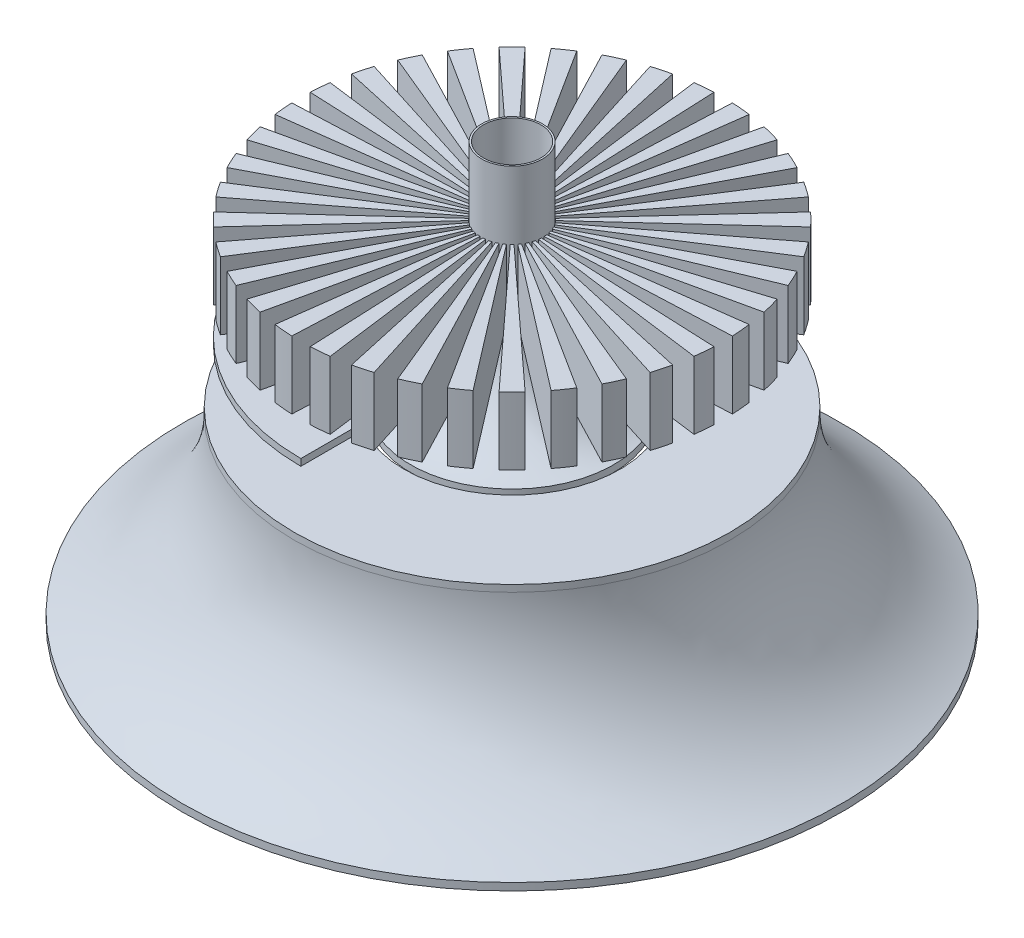
SolidWorks part; units mm, degrees
other "光纤导管"
ref_plane "前视基准面" through (0, 0, 0) normal (0, 0, 1) x (1, 0, 0)
ref_plane "上视基准面" through (0, 0, 0) normal (0, 1, 0) x (1, 0, 0)
ref_plane "右视基准面" through (0, 0, 0) normal (1, 0, 0) x (0, 0, -1)
sketch "草图2" plane through (0, 0, 0) normal (0, 1, 0) x (1, 0, 0)
  circle A0 centre (0, 0) radius 8.5
  circle A1 centre (0, 0) radius 8.5
  circle A2 centre (0, 0) radius 9
extrude "光纤导管" add sketch "草图2" along normal blind 40 contours A2 A0 region at (-8.7454, 0, 0)
sketch "草图5" plane through (0, 0, 0) normal (0, 1, 0) x (1, 0, 0)
  line L0 (0, 23.5527) -> (0, -24.5414) construction
  circle A0 centre (0, 0) radius 9
  circle A1 centre (0, 0) radius 30
sketch "草图6" plane through (0, 0, 0) normal (0, 1, 0) x (1, 0, 0)
  line L0 (0, 0) -> (0, 45.2005) construction
  line L1 (-1.1868, -9.0148) -> (-8.1579, -61.9653)
  line L2 (1.1868, 9.0148) -> (8.1579, 61.9653)
  line L3 (0.3966, 9.0839) -> (2.7262, 62.4405)
  line L4 (1.968, 8.877) -> (13.5275, 61.0185)
  line L5 (2.7342, 8.6717) -> (18.7941, 59.6073)
  line L6 (3.4796, 8.4004) -> (23.9177, 57.7425)
  line L7 (4.1985, 8.0652) -> (28.8593, 55.4382)
  line L8 (4.8854, 7.6686) -> (33.5812, 52.712)
  line L9 (5.5352, 7.2136) -> (38.0476, 49.5846)
  line L10 (8.6717, 2.7342) -> (59.6073, 18.7941)
  line L11 (6.1428, 6.7037) -> (42.2244, 46.0798)
  line L12 (6.7037, 6.1428) -> (46.0798, 42.2244)
  line L13 (7.2136, 5.5352) -> (49.5846, 38.0476)
  line L14 (7.6686, 4.8854) -> (52.712, 33.5812)
  line L15 (7.2136, 5.5352) -> (49.5846, 38.0476)
  line L16 (8.0652, 4.1985) -> (55.4382, 28.8593)
  line L17 (8.4004, 3.4796) -> (57.7425, 23.9177)
  line L18 (8.877, 1.968) -> (61.0185, 13.5275)
  line L19 (9.0148, 1.1868) -> (61.9653, 8.1579)
  line L20 (9.0839, 0.3966) -> (62.4405, 2.7262)
  line L21 (-0.3966, -9.0839) -> (-2.7262, -62.4405)
  line L22 (-1.968, -8.877) -> (-13.5275, -61.0185)
  line L23 (-2.7342, -8.6717) -> (-18.7941, -59.6073)
  line L24 (-3.4796, -8.4004) -> (-23.9177, -57.7425)
  line L25 (-4.1985, -8.0652) -> (-28.8593, -55.4382)
  line L26 (-4.8854, -7.6686) -> (-33.5812, -52.712)
  line L27 (-5.5352, -7.2136) -> (-38.0476, -49.5846)
  line L28 (-8.6717, -2.7342) -> (-59.6073, -18.7941)
  line L29 (-6.1428, -6.7037) -> (-42.2244, -46.0798)
  line L30 (-6.7037, -6.1428) -> (-46.0798, -42.2244)
  line L31 (-7.2136, -5.5352) -> (-49.5846, -38.0476)
  line L32 (-7.6686, -4.8854) -> (-52.712, -33.5812)
  line L33 (-7.2136, -5.5352) -> (-49.5846, -38.0476)
  line L34 (-8.0652, -4.1985) -> (-55.4382, -28.8593)
  line L35 (-8.4004, -3.4796) -> (-57.7425, -23.9177)
  line L36 (-8.877, -1.968) -> (-61.0185, -13.5275)
  line L37 (-9.0148, -1.1868) -> (-61.9653, -8.1579)
  line L38 (-9.0839, -0.3966) -> (-62.4405, -2.7262)
  line L39 (-9.0839, 0.3966) -> (-62.4405, 2.7262)
  line L40 (-9.0148, 1.1868) -> (-61.9653, 8.1579)
  line L41 (-8.877, 1.968) -> (-61.0185, 13.5275)
  line L42 (-8.4004, 3.4796) -> (-57.7425, 23.9177)
  line L43 (-8.0652, 4.1985) -> (-55.4382, 28.8593)
  line L44 (-7.2136, 5.5352) -> (-49.5846, 38.0476)
  line L45 (-7.6686, 4.8854) -> (-52.712, 33.5812)
  line L46 (-7.2136, 5.5352) -> (-49.5846, 38.0476)
  line L47 (-6.7037, 6.1428) -> (-46.0798, 42.2244)
  line L48 (-6.1428, 6.7037) -> (-42.2244, 46.0798)
  line L49 (-8.6717, 2.7342) -> (-59.6073, 18.7941)
  line L50 (-5.5352, 7.2136) -> (-38.0476, 49.5846)
  line L51 (-4.8854, 7.6686) -> (-33.5812, 52.712)
  line L52 (-4.1985, 8.0652) -> (-28.8593, 55.4382)
  line L53 (-3.4796, 8.4004) -> (-23.9177, 57.7425)
  line L54 (-2.7342, 8.6717) -> (-18.7941, 59.6073)
  line L55 (-1.968, 8.877) -> (-13.5275, 61.0185)
  line L56 (-0.3966, 9.0839) -> (-2.7262, 62.4405)
  line L57 (-1.1868, 9.0148) -> (-8.1579, 61.9653)
  line L60 (9.0839, -0.3966) -> (62.4405, -2.7262)
  line L61 (9.0148, -1.1868) -> (61.9653, -8.1579)
  line L62 (8.877, -1.968) -> (61.0185, -13.5275)
  line L63 (8.4004, -3.4796) -> (57.7425, -23.9177)
  line L64 (8.0652, -4.1985) -> (55.4382, -28.8593)
  line L65 (7.2136, -5.5352) -> (49.5846, -38.0476)
  line L66 (7.6686, -4.8854) -> (52.712, -33.5812)
  line L67 (7.2136, -5.5352) -> (49.5846, -38.0476)
  line L68 (6.7037, -6.1428) -> (46.0798, -42.2244)
  line L69 (6.1428, -6.7037) -> (42.2244, -46.0798)
  line L70 (8.6717, -2.7342) -> (59.6073, -18.7941)
  line L71 (5.5352, -7.2136) -> (38.0476, -49.5846)
  line L72 (4.8854, -7.6686) -> (33.5812, -52.712)
  line L73 (4.1985, -8.0652) -> (28.8593, -55.4382)
  line L74 (3.4796, -8.4004) -> (23.9177, -57.7425)
  line L75 (2.7342, -8.6717) -> (18.7941, -59.6073)
  line L76 (1.968, -8.877) -> (13.5275, -61.0185)
  line L77 (0.3966, -9.0839) -> (2.7262, -62.4405)
  line L78 (1.1868, -9.0148) -> (8.1579, -61.9653)
  arc A0 (-62.4405, -2.7262) -> (-61.9653, -8.1579) centre (0, 0) ccw
  arc A1 (62.4405, 2.7262) -> (61.9653, 8.1579) centre (0, 0) ccw
  arc A2 (8.1579, 61.9653) -> (2.7262, 62.4405) centre (0, 0) ccw
  arc A3 (9.0839, 0.3966) -> (9.0148, 1.1868) centre (0, 0) ccw
  arc A4 (18.7941, 59.6073) -> (13.5275, 61.0185) centre (0, 0) ccw
  arc A5 (28.8593, 55.4382) -> (23.9177, 57.7425) centre (0, 0) ccw
  arc A6 (38.0476, 49.5846) -> (33.5812, 52.712) centre (0, 0) ccw
  arc A7 (5.5352, 7.2136) -> (4.8854, 7.6686) centre (0, 0) ccw
  arc A8 (1.1868, 9.0148) -> (0.3966, 9.0839) centre (0, 0) ccw
  arc A9 (2.7342, 8.6717) -> (1.968, 8.877) centre (0, 0) ccw
  arc A10 (4.1985, 8.0652) -> (3.4796, 8.4004) centre (0, 0) ccw
  arc A11 (46.0798, 42.2244) -> (42.2244, 46.0798) centre (0, 0) ccw
  arc A12 (6.7037, 6.1428) -> (6.1428, 6.7037) centre (0, 0) ccw
  arc A13 (52.712, 33.5812) -> (49.5846, 38.0476) centre (0, 0) ccw
  arc A14 (7.6686, 4.8854) -> (7.2136, 5.5352) centre (0, 0) ccw
  arc A15 (57.7425, 23.9177) -> (55.4382, 28.8593) centre (0, 0) ccw
  arc A16 (8.4004, 3.4796) -> (8.0652, 4.1985) centre (0, 0) ccw
  arc A17 (61.0185, 13.5275) -> (59.6073, 18.7941) centre (0, 0) ccw
  arc A18 (8.877, 1.968) -> (8.6717, 2.7342) centre (0, 0) ccw
  arc A19 (-8.1579, -61.9653) -> (-2.7262, -62.4405) centre (0, 0) ccw
  arc A20 (-9.0839, -0.3966) -> (-9.0148, -1.1868) centre (0, 0) ccw
  arc A21 (-18.7941, -59.6073) -> (-13.5275, -61.0185) centre (0, 0) ccw
  arc A22 (-28.8593, -55.4382) -> (-23.9177, -57.7425) centre (0, 0) ccw
  arc A23 (-38.0476, -49.5846) -> (-33.5812, -52.712) centre (0, 0) ccw
  arc A24 (-5.5352, -7.2136) -> (-4.8854, -7.6686) centre (0, 0) ccw
  arc A25 (-1.1868, -9.0148) -> (-0.3966, -9.0839) centre (0, 0) ccw
  arc A26 (-2.7342, -8.6717) -> (-1.968, -8.877) centre (0, 0) ccw
  arc A27 (-4.1985, -8.0652) -> (-3.4796, -8.4004) centre (0, 0) ccw
  arc A28 (-46.0798, -42.2244) -> (-42.2244, -46.0798) centre (0, 0) ccw
  arc A29 (-6.7037, -6.1428) -> (-6.1428, -6.7037) centre (0, 0) ccw
  arc A30 (-52.712, -33.5812) -> (-49.5846, -38.0476) centre (0, 0) ccw
  arc A31 (-7.6686, -4.8854) -> (-7.2136, -5.5352) centre (0, 0) ccw
  arc A32 (-57.7425, -23.9177) -> (-55.4382, -28.8593) centre (0, 0) ccw
  arc A33 (-8.4004, -3.4796) -> (-8.0652, -4.1985) centre (0, 0) ccw
  arc A34 (-61.0185, -13.5275) -> (-59.6073, -18.7941) centre (0, 0) ccw
  arc A35 (-8.877, -1.968) -> (-8.6717, -2.7342) centre (0, 0) ccw
  arc A36 (-8.877, 1.968) -> (-8.6717, 2.7342) centre (0, 0) cw
  arc A37 (-61.0185, 13.5275) -> (-59.6073, 18.7941) centre (0, 0) cw
  arc A38 (-8.4004, 3.4796) -> (-8.0652, 4.1985) centre (0, 0) cw
  arc A39 (-57.7425, 23.9177) -> (-55.4382, 28.8593) centre (0, 0) cw
  arc A40 (-7.6686, 4.8854) -> (-7.2136, 5.5352) centre (0, 0) cw
  arc A41 (-52.712, 33.5812) -> (-49.5846, 38.0476) centre (0, 0) cw
  arc A42 (-6.7037, 6.1428) -> (-6.1428, 6.7037) centre (0, 0) cw
  arc A43 (-46.0798, 42.2244) -> (-42.2244, 46.0798) centre (0, 0) cw
  arc A44 (-4.1985, 8.0652) -> (-3.4796, 8.4004) centre (0, 0) cw
  arc A45 (-2.7342, 8.6717) -> (-1.968, 8.877) centre (0, 0) cw
  arc A46 (-1.1868, 9.0148) -> (-0.3966, 9.0839) centre (0, 0) cw
  arc A47 (-5.5352, 7.2136) -> (-4.8854, 7.6686) centre (0, 0) cw
  arc A48 (-38.0476, 49.5846) -> (-33.5812, 52.712) centre (0, 0) cw
  arc A49 (-28.8593, 55.4382) -> (-23.9177, 57.7425) centre (0, 0) cw
  arc A50 (-18.7941, 59.6073) -> (-13.5275, 61.0185) centre (0, 0) cw
  arc A51 (-9.0839, 0.3966) -> (-9.0148, 1.1868) centre (0, 0) cw
  arc A52 (-8.1579, 61.9653) -> (-2.7262, 62.4405) centre (0, 0) cw
  arc A53 (-62.4405, 2.7262) -> (-61.9653, 8.1579) centre (0, 0) cw
  arc A55 (8.877, -1.968) -> (8.6717, -2.7342) centre (0, 0) cw
  arc A56 (61.0185, -13.5275) -> (59.6073, -18.7941) centre (0, 0) cw
  arc A57 (8.4004, -3.4796) -> (8.0652, -4.1985) centre (0, 0) cw
  arc A58 (57.7425, -23.9177) -> (55.4382, -28.8593) centre (0, 0) cw
  arc A59 (7.6686, -4.8854) -> (7.2136, -5.5352) centre (0, 0) cw
  arc A60 (52.712, -33.5812) -> (49.5846, -38.0476) centre (0, 0) cw
  arc A61 (6.7037, -6.1428) -> (6.1428, -6.7037) centre (0, 0) cw
  arc A62 (46.0798, -42.2244) -> (42.2244, -46.0798) centre (0, 0) cw
  arc A63 (4.1985, -8.0652) -> (3.4796, -8.4004) centre (0, 0) cw
  arc A64 (2.7342, -8.6717) -> (1.968, -8.877) centre (0, 0) cw
  arc A65 (1.1868, -9.0148) -> (0.3966, -9.0839) centre (0, 0) cw
  arc A66 (5.5352, -7.2136) -> (4.8854, -7.6686) centre (0, 0) cw
  arc A67 (38.0476, -49.5846) -> (33.5812, -52.712) centre (0, 0) cw
  arc A68 (28.8593, -55.4382) -> (23.9177, -57.7425) centre (0, 0) cw
  arc A69 (18.7941, -59.6073) -> (13.5275, -61.0185) centre (0, 0) cw
  arc A70 (9.0839, -0.3966) -> (9.0148, -1.1868) centre (0, 0) cw
  arc A71 (8.1579, -61.9653) -> (2.7262, -62.4405) centre (0, 0) cw
  arc A72 (62.4405, -2.7262) -> (61.9653, -8.1579) centre (0, 0) cw
extrude "散热片" add sketch "草图6" along normal blind 20 contours A8 L2 A2 L3 | A9 L5 A4 L4 | A10 L7 A5 L6 | A7 L9 A6 L8 | A12 L12 A11 L11 | A14 L14 A13 L13 | A16 L17 A15 L16 | A18 L18 A17 L10 | A56 L62 A55 L70 | A58 L63 A57 L64 | A60 L66 A59 L65 | A62 L68 A61 L69 | A71 L78 A65 L77 | A52 L57 A46 L56 | A50 L54 A45 L55 | A49 L52 A44 L53 | A48 L50 A47 L51 | A43 L47 A42 L48 | A41 L45 A40 L44 | A39 L42 A38 L43 | A37 L41 A36 L49 | A53 L39 A51 L40 | A20 L38 A0 L37 | A35 L36 A34 L28 | A33 L35 A32 L34 | A31 L32 A30 L31 | A29 L30 A28 L29 | A24 L27 A23 L26 | A27 L25 A22 L24 | A26 L23 A21 L22 | A25 L1 A19 L21 | L19 A1 L20 A3 | L60 A72 L61 A70 | L71 A67 L72 A66 | L73 A68 L74 A63 | L75 A69 L76 A64 region at (-3.6974, 0, 42.2616) region at (3.6974, 0, -42.2616) region at (10.9799, 0, -40.9775) region at (17.9288, 0, -38.4484) region at (24.3329, 0, -34.7509) region at (40.9775, 0, -10.9799) region at (29.9976, 0, -29.9976) region at (34.7509, 0, -24.3329) region at (38.4484, 0, -17.9288) region at (-10.9799, 0, 40.9775) region at (-17.9288, 0, 38.4484) region at (-24.3329, 0, 34.7509) region at (-40.9775, 0, 10.9799) region at (-29.9976, 0, 29.9976) region at (-34.7509, 0, 24.3329) region at (-38.4484, 0, 17.9288) region at (-42.2616, 0, 3.6974) region at (-42.2616, 0, -3.6974) region at (-40.9775, 0, -10.9799) region at (-38.4484, 0, -17.9288) region at (-34.7509, 0, -24.3329) region at (-29.9976, 0, -29.9976) region at (-24.3329, 0, -34.7509) region at (-17.9288, 0, -38.4484) region at (-10.9799, 0, -40.9775) region at (-3.6974, 0, -42.2616) region at (40.9775, 0, 10.9799) region at (38.4484, 0, 17.9288) region at (34.7509, 0, 24.3329) region at (29.9976, 0, 29.9976) region at (3.6974, 0, 42.2616)
sketch "草图21" plane through (0, 0, 0) normal (0, 1, 0) x (1, 0, 0)
  line L0 (0, -32) -> (0, -62.5)
  line L1 (0, 32) -> (0, 62.5)
  arc A0 (0, 32) -> (0, -32) centre (0, 0) ccw
  arc A1 (0, 62.5) -> (0, -62.5) centre (0, 0) ccw
extrude "凸台-拉伸6" add sketch "草图21" against normal blind 2 from offset 10 separate body offset against normal yes
sketch "草图12" plane through (0, 0, 0) normal (1, 0, 0) x (0, 0, -1)
  line L0 (0, 0) -> (0, 39.2195) construction
  line L1 (18.9129, 20) -> (62.5, 20)
  line L2 (62.5, 20) -> (62.5, 0)
  line L3 (18.7941, 20) -> (18.9129, 20)
  arc A0 (18.7941, 20) -> (62.5, 0) centre (18.7941, -37.7551) cw
sketch "草图13" plane through (0, 0, 0) normal (0, 1, 0) x (1, 0, 0)
  circle A0 centre (0, 0) radius 62.5
  circle A1 centre (0, 0) radius 97.5
  circle A2 centre (0, 0) radius 8.5
sketch "草图14" plane through (0, 0, 0) normal (0, 1, 0) x (1, 0, 0)
  circle A0 centre (0, 0) radius 8.5
extrude "凸台-拉伸1" add sketch "草图14" against normal blind 2 separate body
sketch "草图16" plane through (0, 0, 0) normal (0, 0, 1) x (1, 0, 0)
  line L0 (0, 0) -> (0, -29.8666)
  line L1 (0, 0) -> (9, 0)
  line L2 (0, -29.8666) -> (30, -29.8666)
  line L3 (30, -27.8666) -> (30, -29.8666)
  line L4 (0, 0) -> (0, 50000) construction
  arc A0 (9, 0) -> (30, -27.8666) centre (37.9892, 0) ccw
revolve "自然光透镜" add sketch "草图16" angle 360 about L4
sketch "草图17" plane through (0, 0, 0) normal (0, 1, 0) x (1, 0, 0)
  circle A0 centre (0, 0) radius 32
  circle A1 centre (0, 0) radius 62.5
extrude "LED面板" add sketch "草图17" along normal blind 2 from offset 30 separate body offset against normal yes
sketch "草图19" plane through (0, 0, 0) normal (0, 1, 0) x (1, 0, 0)
  line L0 (0, 0) -> (50000, 0) construction
  line L1 (0, 0) -> (0, -50000) construction
  line L2 (0, 0) -> (19134.1716, -46193.9766) construction
  line L3 (0, 0) -> (44350.5417, -23087.4307) construction
  circle A3 centre (0, 0) radius 47 construction
  circle A4 centre (17.9861, -43.4223) radius 5
  circle A5 centre (41.6895, -21.7022) radius 5
  circle A6 centre (-41.6895, -21.7022) radius 5
  circle A7 centre (-17.9861, -43.4223) radius 5
  circle A8 centre (-41.6895, 21.7022) radius 5
  circle A9 centre (-17.9861, 43.4223) radius 5
  circle A10 centre (17.9861, 43.4223) radius 5
  circle A11 centre (41.6895, 21.7022) radius 5
extrude "凸台-拉伸5" add sketch "草图19" against normal blind 2 from offset 30 offset against normal yes
sketch "草图20" plane through (0, 0, 0) normal (0, 1, 0) x (1, 0, 0)
  line L0 (0, -32) -> (0, -62.5)
  line L1 (0, 32) -> (0, 62.5)
  arc A0 (0, 32) -> (0, -32) centre (0, 0) ccw
  arc A1 (0, 62.5) -> (0, -62.5) centre (0, 0) ccw
sketch "草图23" plane through (0, 0, 0) normal (0, 0, 1) x (1, 0, 0)
  line L0 (0, 0) -> (0, -50000) construction
  line L1 (62.4039, -1028) -> (62.4039, 48972) construction
  line L2 (64.4039, -30) -> (64.4039, -28)
  line L4 (62.4039, -28) -> (64.4039, -28)
  line L5 (62.4039, -30) -> (62.4039, -28)
  line L6 (97.4986, -83.1125) -> (97.4986, -80.9311)
  line L7 (97.4986, -77.9592) -> (97.4986, 49000) construction
  line L8 (-62.5, -30) -> (62.5, -30) construction
  line L9 (62.5, -28) -> (-62.5, -28) construction
  arc A0 (62.4039, -30) -> (97.4986, -83.1125) centre (120.1415, -30) ccw
  arc A1 (64.4039, -30) -> (97.4986, -80.9311) centre (120.1415, -30) ccw
  arc A2 (64.4039, -30) -> (98.283, -81.2727) centre (120.1415, -30) ccw construction
  dimension "D1" = 2
revolve "旋转1" add sketch "草图23" angle 360 about L0
